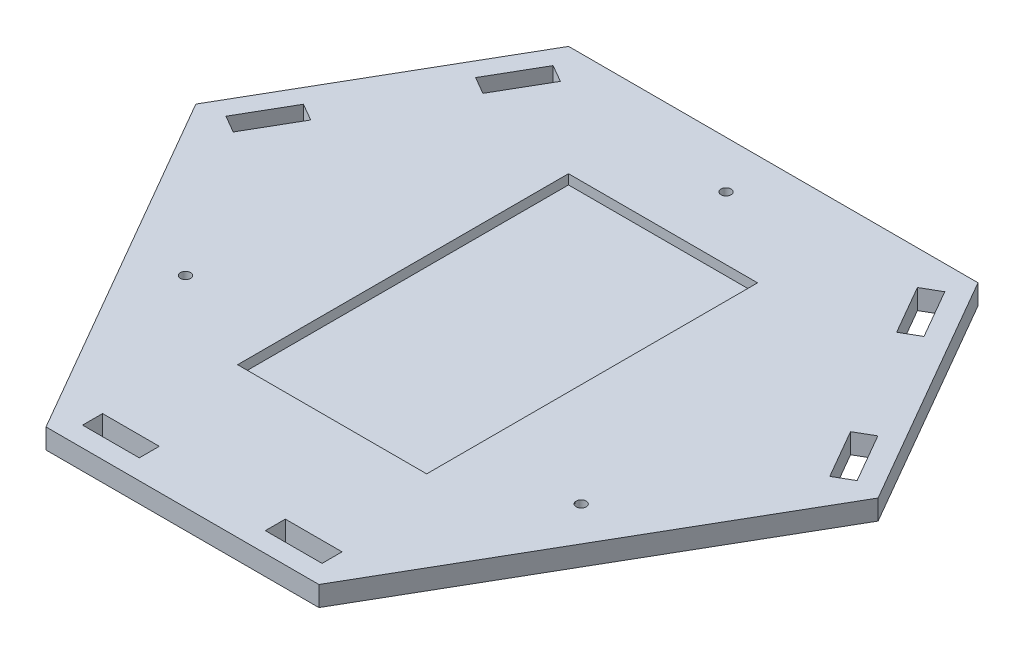
SolidWorks part; units mm, degrees
ref_plane "Front Plane" through (0, 0, 0) normal (0, 0, 1) x (1, 0, 0)
ref_plane "Top Plane" through (0, 0, 0) normal (0, 1, 0) x (1, 0, 0)
ref_plane "Right Plane" through (0, 0, 0) normal (1, 0, 0) x (0, 0, -1)
sketch "Sketch1" plane through (0, 0, 0) normal (0, 1, 0) x (1, 0, 0)
  line L0 (0, 200) -> (-173.2051, -100)
  line L1 (-173.2051, -100) -> (173.2051, -100)
  line L2 (173.2051, -100) -> (0, 200)
  line L4 (0, -175) -> (151.5544, 87.5)
  line L5 (151.5544, 87.5) -> (-151.5544, 87.5)
  line L6 (-151.5544, 87.5) -> (0, -175)
  circle A0 centre (0, 0) radius 200 construction
  circle A1 centre (0, 0) radius 100 construction
  circle A2 centre (0, 0) radius 175 construction
  circle A3 centre (0, 0) radius 87.5 construction
  dimension "D1" = 400
  dimension "D2" = 350
other "AlignGroup1"
extrude "Boss-Extrude1" add sketch "Sketch1" along normal blind 6.35 contours L0 L6 L1 L4 L2 L5 region at (0, 0, 0)
sketch "Sketch2" plane through (0, 6.35, 0) normal (0, 1, 0) x (1, 0, 0)
  line L0 (-43.3013, -100) -> (43.3013, -100) construction
  line L1 (-38, -87.35) -> (-20, -87.35)
  line L2 (-38, -87.35) -> (-38, -93.7)
  line L3 (-38, -93.7) -> (-20, -93.7)
  line L4 (-20, -87.35) -> (-20, -93.7)
  line L5 (0, -100) -> (0, 87.5) construction
  line L6 (64.9519, 87.5) -> (-64.9519, 87.5) construction
  line L7 (38, -87.35) -> (38, -93.7)
  line L8 (-86.6025, 50) -> (75.7772, -43.75) construction
  line L9 (-62.1466, 79.759) -> (-56.6473, 76.584)
  line L10 (20, -87.35) -> (20, -93.7)
  line L11 (-62.1466, 79.759) -> (-71.1466, 64.1705)
  line L12 (-71.1466, 64.1705) -> (-65.6473, 60.9955)
  line L13 (38, -93.7) -> (20, -93.7)
  line L14 (38, -87.35) -> (20, -87.35)
  line L15 (-56.6473, 76.584) -> (-65.6473, 60.9955)
  line L16 (-64.9519, 87.5) -> (-108.2532, 12.5) construction
  line L17 (43.3013, -100) -> (108.2532, 12.5) construction
  line L18 (-94.6473, 10.766) -> (-85.6473, 26.3545)
  line L19 (-91.1466, 29.5295) -> (-85.6473, 26.3545)
  line L20 (-100.1466, 13.941) -> (-91.1466, 29.5295)
  line L21 (-100.1466, 13.941) -> (-94.6473, 10.766)
  line L22 (86.6025, 50) -> (-75.7772, -43.75) construction
  line L23 (108.2532, 12.5) -> (64.9519, 87.5) construction
  line L24 (-108.2532, 12.5) -> (-43.3013, -100) construction
  line L25 (100.1466, 13.941) -> (91.1466, 29.5295)
  line L26 (56.6473, 76.584) -> (62.1466, 79.759)
  line L27 (56.6473, 76.584) -> (65.6473, 60.9955)
  line L28 (65.6473, 60.9955) -> (71.1466, 64.1705)
  line L29 (62.1466, 79.759) -> (71.1466, 64.1705)
  line L30 (85.6473, 26.3545) -> (91.1466, 29.5295)
  line L31 (94.6473, 10.766) -> (85.6473, 26.3545)
  line L32 (94.6473, 10.766) -> (100.1466, 13.941)
  point P4 (-29, -93.7)
  dimension "D1" = 18
  dimension "D2" = 6.35
  dimension "D3" = 6.3
  dimension "D4" = 38
  dimension "D5" = 6.3
  dimension "D6" = 18
  dimension "D7" = 6.35
  dimension "D8" = 38
  dimension "D9" = 18
  dimension "D10" = 6.35
  dimension "D11" = 38
  dimension "D12" = 6.3
extrude "Cut-Extrude1" cut sketch "Sketch2" against normal through all
sketch "Sketch3" plane through (0, 6.35, 0) normal (0, 1, 0) x (1, 0, 0)
  point P0 (0, 0)
ref_axis "Axis1" through (0, 0, 0) along (0, 1, 0)
sketch "Sketch4" plane through (0, 6.35, 0) normal (0, 1, 0) x (1, 0, 0)
  line L0 (-30, 52.5) -> (30, 52.5)
  line L1 (30, 52.5) -> (30, -52.5)
  line L2 (30, -52.5) -> (-30, -52.5)
  line L3 (-30, -52.5) -> (-30, 52.5)
  point P4 (0, 52.5)
  point P6 (-30, 0)
  dimension "D1" = 60
  dimension "D2" = 105
extrude "Cut-Extrude2" cut sketch "Sketch4" against normal blind 3.1
sketch "Sketch5" plane through (0, 6.35, 0) normal (0, 1, 0) x (1, 0, 0)
  line L0 (0, 87.5) -> (0, 57.5) construction
  line L1 (64.9519, 87.5) -> (-64.9519, 87.5) construction
  line L2 (-75.7772, -43.75) -> (-62.7868, -36.25) construction
  line L3 (-108.2532, 12.5) -> (-43.3013, -100) construction
  line L4 (75.7772, -43.75) -> (62.7868, -36.25) construction
  line L5 (43.3013, -100) -> (108.2532, 12.5) construction
  circle A0 centre (0, 0) radius 57.5 construction
  circle A1 centre (0, 0) radius 72.5 construction
  circle A2 centre (0, 72.5) radius 1.6
  circle A3 centre (-62.7868, -36.25) radius 1.6
  circle A4 centre (62.7868, -36.25) radius 1.6
  point P8 (0, 72.5)
  dimension "D1" = 115
  dimension "D2" = 3.2
extrude "Cut-Extrude3" cut sketch "Sketch5" against normal through all
